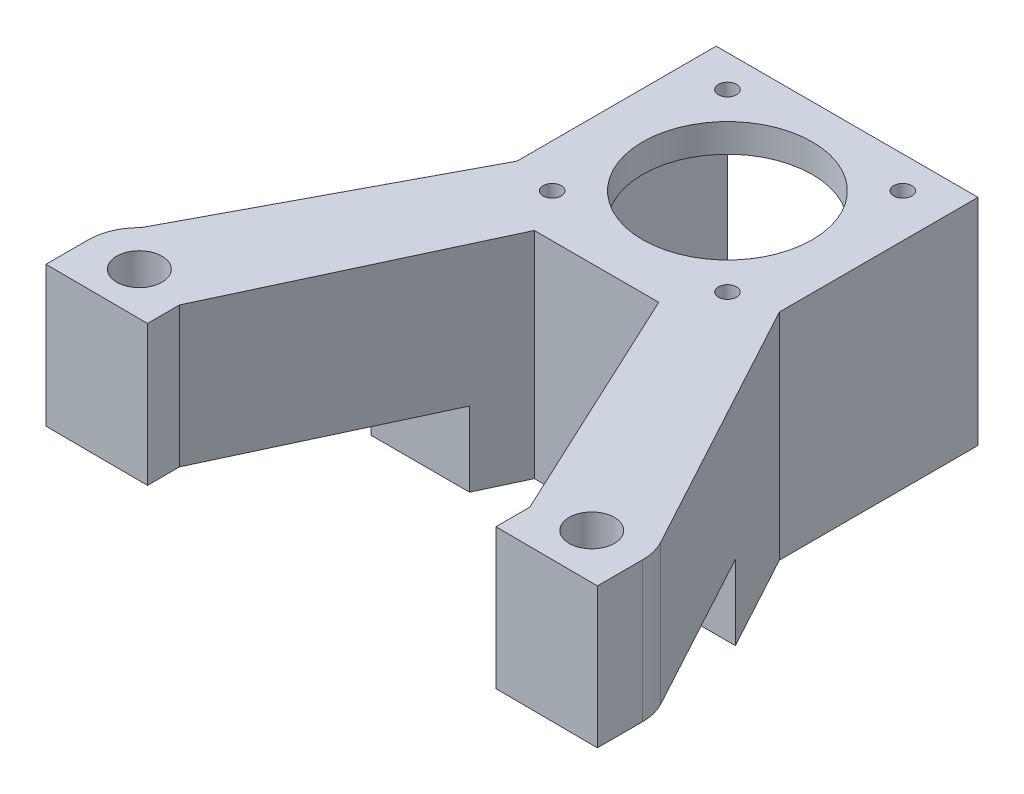
SolidWorks part; units mm, degrees
note: The reader was unsure of these and kept them because the rebuilt part matched: shared geometry of "草图7<7>", "草图7<8>".
ref_plane "前视基准面" through (0, 0, 0) normal (0, 0, 1) x (1, 0, 0)
ref_plane "上视基准面" through (0, 0, 0) normal (0, 1, 0) x (1, 0, 0)
ref_plane "右视基准面" through (0, 0, 0) normal (1, 0, 0) x (0, 0, -1)
sketch "草图6" plane through (0, 0, 0) normal (0, 1, 0) x (1, 0, 0)
  line L1 (-21.15, -21.15) -> (21.15, -21.15)
  line L2 (-21.15, -21.15) -> (-21.15, 21.15)
  line L3 (-21.15, 21.15) -> (21.15, 21.15)
  line L5 (0, 21.15) -> (0, -21.15) construction
  line L6 (-21.15, 0) -> (21.15, 0) construction
  line L8 (21.15, 21.15) -> (21.15, -21.15)
  circle A0 centre (15.5, 15.5) radius 1.6
  circle A1 centre (-15.5, 15.5) radius 1.6
  circle A2 centre (-15.5, -15.5) radius 1.6
  circle A3 centre (15.5, -15.5) radius 1.6
  circle A4 centre (0, 0) radius 15
  point P0 (0, 0)
extrude "凸台-拉伸1" add sketch "草图6" along normal blind 5
sketch "草图7" plane through (0, 5, 0) normal (0, 1, 0) x (1, 0, 0)
  line L0 (49, -65) -> (49, -72)
  line L1 (30.9639, -71.908) -> (49, -72)
  line L2 (21, -10) -> (47.9146, -59.7152)
  line L3 (49, -64) -> (49, -65)
  line L4 (-10, -21) -> (-30.9639, -65.9194)
  line L5 (-21, -10) -> (-46.2023, -57.4784)
  line L6 (10, -21) -> (30.9639, -65.9194)
  line L7 (30.9639, -71.908) -> (30.9639, -65.9194)
  line L8 (-49, -64) -> (-49, -71.5)
  line L9 (-30.9639, -65.9194) -> (-30.9639, -71.592)
  line L10 (-49, -71.5) -> (-30.9639, -71.592)
  arc A0 (-46.2023, -57.4784) -> (-49, -64) centre (-40, -64) ccw
  arc A1 (49, -64) -> (47.9146, -59.7152) centre (40, -64) ccw
  circle A2 centre (-40, -64) radius 4
  circle A3 centre (40, -64) radius 4
  dimension "D1" = 18
  dimension "D2" = 18
  dimension "D3" = 8
  dimension "D4" = 8
extrude "凸台-拉伸5" add sketch "草图7" against normal blind 38
extrude "凸台-拉伸7" add sketch "草图7<7>" against normal blind 38 contours A1 A3
sketch "草图7<7>" plane through (0, 5, 0) normal (0, 1, 0) x (1, 0, 0) same geometry as "草图7"
extrude "凸台-拉伸8" add sketch "草图7<8>" against normal blind 38 contours A0 A2
sketch "草图7<8>" plane through (0, 5, 0) normal (0, 1, 0) x (1, 0, 0) same geometry as "草图7"
sketch "草图12" plane through (0, 5, 0) normal (0, 1, 0) x (1, 0, 0)
  line L0 (21.15, 21.15) -> (23.15, 21.15)
  line L1 (21.15, 21.15) -> (21.15, -23.15)
  line L2 (23.15, 21.15) -> (23.15, -23.15)
  line L3 (21.15, -23.15) -> (23.15, -23.15)
extrude "凸台-拉伸11" add sketch "草图12" against normal blind 38
sketch "草图14" plane through (0, 5, 0) normal (0, 1, 0) x (1, 0, 0)
  line L0 (21.15, -23.15) -> (-23.15, -23.15)
  line L1 (21.15, -23.15) -> (21.15, -21.15)
  line L2 (-23.15, -23.15) -> (-23.15, -21.15)
  line L3 (21.15, -21.15) -> (-23.15, -21.15)
extrude "凸台-拉伸12" add sketch "草图14" against normal blind 38
sketch "草图15" plane through (0, 5, 0) normal (0, 1, 0) x (1, 0, 0)
  line L0 (-23.15, -21.15) -> (-23.15, 21.15)
  line L1 (-23.15, -21.15) -> (-21.15, -21.15)
  line L2 (-23.15, 21.15) -> (-21.15, 21.15)
  line L3 (-21.15, -21.15) -> (-21.15, 21.15)
extrude "凸台-拉伸13" add sketch "草图15" against normal blind 38
sketch "草图17" plane through (0, -33, 0) normal (0, -1, 0) x (1, 0, 0)
  line L1 (62.0405, 30.9533) -> (-8.6048, 30.9533)
  line L2 (62.0405, 30.9533) -> (62.0405, 85.063)
  line L3 (62.0405, 85.063) -> (-8.6048, 85.063)
  line L5 (-8.6048, 30.9533) -> (-61.8372, 30.9533)
  line L7 (-8.6048, 85.063) -> (-61.8372, 85.063)
  line L8 (-61.8372, 30.9533) -> (-61.8372, 85.063)
extrude "切除-拉伸1" cut sketch "草图17" against normal blind 13.2
